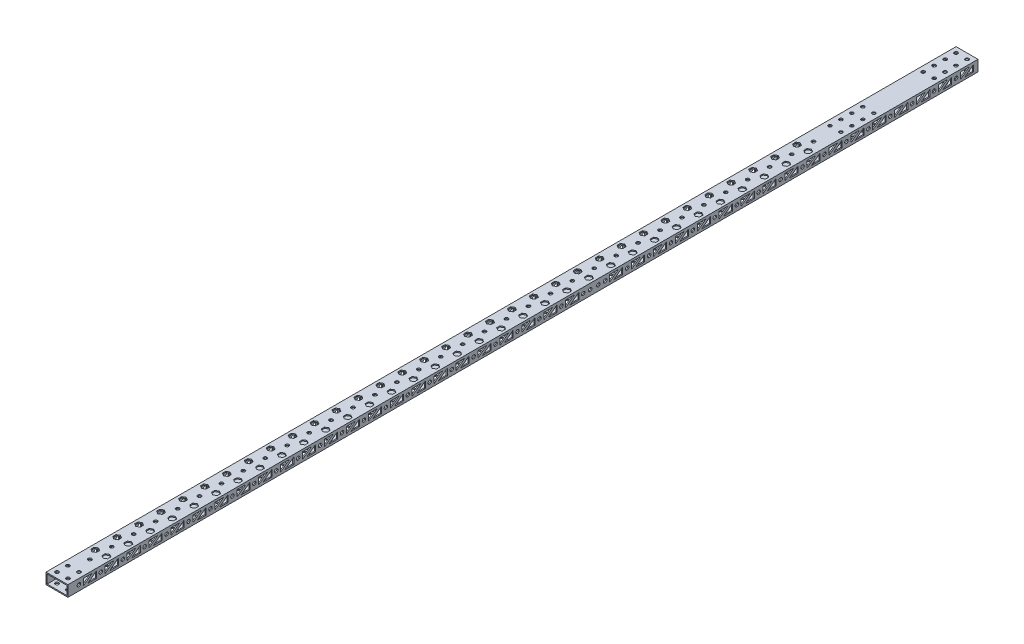
SolidWorks part; units mm, degrees
ref_plane "前视基准面" through (0, 0, 0) normal (0, 0, 1) x (1, 0, 0)
ref_plane "上视基准面" through (0, 0, 0) normal (0, 1, 0) x (1, 0, 0)
ref_plane "右视基准面" through (0, 0, 0) normal (1, 0, 0) x (0, 0, -1)
other "Configuration Table"
sketch "草图1" plane through (0, 0, 0) normal (0, 0, 1) x (1, 0, 0)
  line L1 (0, 0) -> (20, 0)
  line L2 (0, 0) -> (0, -10)
  line L3 (0, -10) -> (20, -10)
  line L4 (20, 0) -> (20, -10)
  dimension "D1" = 20
  dimension "D2" = 10
extrude "拉伸-薄壁1" add sketch "草图1" along normal blind 830 thin thin type one direction reverse wall 1
sketch "草图2" plane through (0, -10, 0) normal (0, -1, 0) x (1, 0, 0)
  line L0 (20, 10) -> (0, 10) construction
  line L1 (20, 830) -> (20, 0) construction
  line L2 (0, 830) -> (0, 0) construction
  line L3 (10, 0) -> (10, 10) construction
  line L4 (0, 0) -> (20, 0) construction
  line L5 (10, 10) -> (10, 140) construction
  line L6 (0, 415) -> (20, 415) construction
  line L7 (10, 830) -> (10, 820) construction
  line L8 (20, 820) -> (0, 820) construction
  line L9 (0, 115) -> (20, 115) construction
  line L10 (20, 105) -> (0, 105) construction
  line L11 (0, 20) -> (20, 20) construction
  line L12 (10, 800) -> (10, 780) construction
  line L13 (15.0981, 787) -> (17.6962, 788.5)
  line L14 (17.6962, 788.5) -> (17.6962, 791.5)
  line L15 (17.6962, 791.5) -> (15.0981, 793)
  line L16 (15.0981, 793) -> (12.5, 791.5)
  line L17 (12.5, 791.5) -> (12.5, 788.5)
  line L18 (12.5, 788.5) -> (15.0981, 787)
  line L19 (15.0981, 790) -> (10, 790) construction
  line L20 (7.5, 788.5) -> (4.9019, 787)
  line L21 (7.5, 791.5) -> (7.5, 788.5)
  line L22 (4.9019, 793) -> (7.5, 791.5)
  line L23 (2.3038, 791.5) -> (4.9019, 793)
  line L24 (2.3038, 788.5) -> (2.3038, 791.5)
  line L25 (4.9019, 787) -> (2.3038, 788.5)
  line L26 (2.3038, 771.5) -> (4.9019, 773)
  line L27 (4.9019, 773) -> (7.5, 771.5)
  line L28 (4.9019, 767) -> (2.3038, 768.5)
  line L29 (2.3038, 768.5) -> (2.3038, 771.5)
  line L30 (7.5, 768.5) -> (4.9019, 767)
  line L31 (7.5, 771.5) -> (7.5, 768.5)
  line L32 (15.0981, 773) -> (12.5, 771.5)
  line L33 (17.6962, 771.5) -> (15.0981, 773)
  line L34 (17.6962, 768.5) -> (17.6962, 771.5)
  line L35 (15.0981, 767) -> (17.6962, 768.5)
  line L36 (12.5, 768.5) -> (15.0981, 767)
  line L37 (12.5, 771.5) -> (12.5, 768.5)
  line L38 (2.3038, 751.5) -> (4.9019, 753)
  line L39 (4.9019, 753) -> (7.5, 751.5)
  line L40 (4.9019, 747) -> (2.3038, 748.5)
  line L41 (2.3038, 748.5) -> (2.3038, 751.5)
  line L42 (7.5, 748.5) -> (4.9019, 747)
  line L43 (7.5, 751.5) -> (7.5, 748.5)
  line L44 (15.0981, 753) -> (12.5, 751.5)
  line L45 (17.6962, 751.5) -> (15.0981, 753)
  line L46 (17.6962, 748.5) -> (17.6962, 751.5)
  line L47 (15.0981, 747) -> (17.6962, 748.5)
  line L48 (12.5, 748.5) -> (15.0981, 747)
  line L49 (12.5, 751.5) -> (12.5, 748.5)
  line L50 (2.3038, 731.5) -> (4.9019, 733)
  line L51 (4.9019, 733) -> (7.5, 731.5)
  line L52 (4.9019, 727) -> (2.3038, 728.5)
  line L53 (2.3038, 728.5) -> (2.3038, 731.5)
  line L54 (7.5, 728.5) -> (4.9019, 727)
  line L55 (7.5, 731.5) -> (7.5, 728.5)
  line L56 (15.0981, 733) -> (12.5, 731.5)
  line L57 (17.6962, 731.5) -> (15.0981, 733)
  line L58 (17.6962, 728.5) -> (17.6962, 731.5)
  line L59 (15.0981, 727) -> (17.6962, 728.5)
  line L60 (12.5, 728.5) -> (15.0981, 727)
  line L61 (12.5, 731.5) -> (12.5, 728.5)
  line L62 (2.3038, 711.5) -> (4.9019, 713)
  line L63 (4.9019, 713) -> (7.5, 711.5)
  line L64 (4.9019, 707) -> (2.3038, 708.5)
  line L65 (2.3038, 708.5) -> (2.3038, 711.5)
  line L66 (7.5, 708.5) -> (4.9019, 707)
  line L67 (7.5, 711.5) -> (7.5, 708.5)
  line L68 (15.0981, 713) -> (12.5, 711.5)
  line L69 (17.6962, 711.5) -> (15.0981, 713)
  line L70 (17.6962, 708.5) -> (17.6962, 711.5)
  line L71 (15.0981, 707) -> (17.6962, 708.5)
  line L72 (12.5, 708.5) -> (15.0981, 707)
  line L73 (12.5, 711.5) -> (12.5, 708.5)
  line L74 (2.3038, 691.5) -> (4.9019, 693)
  line L75 (4.9019, 693) -> (7.5, 691.5)
  line L76 (4.9019, 687) -> (2.3038, 688.5)
  line L77 (2.3038, 688.5) -> (2.3038, 691.5)
  line L78 (7.5, 688.5) -> (4.9019, 687)
  line L79 (7.5, 691.5) -> (7.5, 688.5)
  line L80 (15.0981, 693) -> (12.5, 691.5)
  line L81 (17.6962, 691.5) -> (15.0981, 693)
  line L82 (17.6962, 688.5) -> (17.6962, 691.5)
  line L83 (15.0981, 687) -> (17.6962, 688.5)
  line L84 (12.5, 688.5) -> (15.0981, 687)
  line L85 (12.5, 691.5) -> (12.5, 688.5)
  line L86 (2.3038, 671.5) -> (4.9019, 673)
  line L87 (4.9019, 673) -> (7.5, 671.5)
  line L88 (4.9019, 667) -> (2.3038, 668.5)
  line L89 (2.3038, 668.5) -> (2.3038, 671.5)
  line L90 (7.5, 668.5) -> (4.9019, 667)
  line L91 (7.5, 671.5) -> (7.5, 668.5)
  line L92 (15.0981, 673) -> (12.5, 671.5)
  line L93 (17.6962, 671.5) -> (15.0981, 673)
  line L94 (17.6962, 668.5) -> (17.6962, 671.5)
  line L95 (15.0981, 667) -> (17.6962, 668.5)
  line L96 (12.5, 668.5) -> (15.0981, 667)
  line L97 (12.5, 671.5) -> (12.5, 668.5)
  line L98 (2.3038, 651.5) -> (4.9019, 653)
  line L99 (4.9019, 653) -> (7.5, 651.5)
  line L100 (4.9019, 647) -> (2.3038, 648.5)
  line L101 (2.3038, 648.5) -> (2.3038, 651.5)
  line L102 (7.5, 648.5) -> (4.9019, 647)
  line L103 (7.5, 651.5) -> (7.5, 648.5)
  line L104 (15.0981, 653) -> (12.5, 651.5)
  line L105 (17.6962, 651.5) -> (15.0981, 653)
  line L106 (17.6962, 648.5) -> (17.6962, 651.5)
  line L107 (15.0981, 647) -> (17.6962, 648.5)
  line L108 (12.5, 648.5) -> (15.0981, 647)
  line L109 (12.5, 651.5) -> (12.5, 648.5)
  line L110 (2.3038, 631.5) -> (4.9019, 633)
  line L111 (4.9019, 633) -> (7.5, 631.5)
  line L112 (4.9019, 627) -> (2.3038, 628.5)
  line L113 (2.3038, 628.5) -> (2.3038, 631.5)
  line L114 (7.5, 628.5) -> (4.9019, 627)
  line L115 (7.5, 631.5) -> (7.5, 628.5)
  line L116 (15.0981, 633) -> (12.5, 631.5)
  line L117 (17.6962, 631.5) -> (15.0981, 633)
  line L118 (17.6962, 628.5) -> (17.6962, 631.5)
  line L119 (15.0981, 627) -> (17.6962, 628.5)
  line L120 (12.5, 628.5) -> (15.0981, 627)
  line L121 (12.5, 631.5) -> (12.5, 628.5)
  line L122 (2.3038, 611.5) -> (4.9019, 613)
  line L123 (4.9019, 613) -> (7.5, 611.5)
  line L124 (4.9019, 607) -> (2.3038, 608.5)
  line L125 (2.3038, 608.5) -> (2.3038, 611.5)
  line L126 (7.5, 608.5) -> (4.9019, 607)
  line L127 (7.5, 611.5) -> (7.5, 608.5)
  line L128 (15.0981, 613) -> (12.5, 611.5)
  line L129 (17.6962, 611.5) -> (15.0981, 613)
  line L130 (17.6962, 608.5) -> (17.6962, 611.5)
  line L131 (15.0981, 607) -> (17.6962, 608.5)
  line L132 (12.5, 608.5) -> (15.0981, 607)
  line L133 (12.5, 611.5) -> (12.5, 608.5)
  line L134 (2.3038, 591.5) -> (4.9019, 593)
  line L135 (4.9019, 593) -> (7.5, 591.5)
  line L136 (4.9019, 587) -> (2.3038, 588.5)
  line L137 (2.3038, 588.5) -> (2.3038, 591.5)
  line L138 (7.5, 588.5) -> (4.9019, 587)
  line L139 (7.5, 591.5) -> (7.5, 588.5)
  line L140 (15.0981, 593) -> (12.5, 591.5)
  line L141 (17.6962, 591.5) -> (15.0981, 593)
  line L142 (17.6962, 588.5) -> (17.6962, 591.5)
  line L143 (15.0981, 587) -> (17.6962, 588.5)
  line L144 (12.5, 588.5) -> (15.0981, 587)
  line L145 (12.5, 591.5) -> (12.5, 588.5)
  line L146 (2.3038, 571.5) -> (4.9019, 573)
  line L147 (4.9019, 573) -> (7.5, 571.5)
  line L148 (4.9019, 567) -> (2.3038, 568.5)
  line L149 (2.3038, 568.5) -> (2.3038, 571.5)
  line L150 (7.5, 568.5) -> (4.9019, 567)
  line L151 (7.5, 571.5) -> (7.5, 568.5)
  line L152 (15.0981, 573) -> (12.5, 571.5)
  line L153 (17.6962, 571.5) -> (15.0981, 573)
  line L154 (17.6962, 568.5) -> (17.6962, 571.5)
  line L155 (15.0981, 567) -> (17.6962, 568.5)
  line L156 (12.5, 568.5) -> (15.0981, 567)
  line L157 (12.5, 571.5) -> (12.5, 568.5)
  line L158 (2.3038, 551.5) -> (4.9019, 553)
  line L159 (4.9019, 553) -> (7.5, 551.5)
  line L160 (4.9019, 547) -> (2.3038, 548.5)
  line L161 (2.3038, 548.5) -> (2.3038, 551.5)
  line L162 (7.5, 548.5) -> (4.9019, 547)
  line L163 (7.5, 551.5) -> (7.5, 548.5)
  line L164 (15.0981, 553) -> (12.5, 551.5)
  line L165 (17.6962, 551.5) -> (15.0981, 553)
  line L166 (17.6962, 548.5) -> (17.6962, 551.5)
  line L167 (15.0981, 547) -> (17.6962, 548.5)
  line L168 (12.5, 548.5) -> (15.0981, 547)
  line L169 (12.5, 551.5) -> (12.5, 548.5)
  line L170 (2.3038, 531.5) -> (4.9019, 533)
  line L171 (4.9019, 533) -> (7.5, 531.5)
  line L172 (4.9019, 527) -> (2.3038, 528.5)
  line L173 (2.3038, 528.5) -> (2.3038, 531.5)
  line L174 (7.5, 528.5) -> (4.9019, 527)
  line L175 (7.5, 531.5) -> (7.5, 528.5)
  line L176 (15.0981, 533) -> (12.5, 531.5)
  line L177 (17.6962, 531.5) -> (15.0981, 533)
  line L178 (17.6962, 528.5) -> (17.6962, 531.5)
  line L179 (15.0981, 527) -> (17.6962, 528.5)
  line L180 (12.5, 528.5) -> (15.0981, 527)
  line L181 (12.5, 531.5) -> (12.5, 528.5)
  line L182 (2.3038, 511.5) -> (4.9019, 513)
  line L183 (4.9019, 513) -> (7.5, 511.5)
  line L184 (4.9019, 507) -> (2.3038, 508.5)
  line L185 (2.3038, 508.5) -> (2.3038, 511.5)
  line L186 (7.5, 508.5) -> (4.9019, 507)
  line L187 (7.5, 511.5) -> (7.5, 508.5)
  line L188 (15.0981, 513) -> (12.5, 511.5)
  line L189 (17.6962, 511.5) -> (15.0981, 513)
  line L190 (17.6962, 508.5) -> (17.6962, 511.5)
  line L191 (15.0981, 507) -> (17.6962, 508.5)
  line L192 (12.5, 508.5) -> (15.0981, 507)
  line L193 (12.5, 511.5) -> (12.5, 508.5)
  line L194 (2.3038, 491.5) -> (4.9019, 493)
  line L195 (4.9019, 493) -> (7.5, 491.5)
  line L196 (4.9019, 487) -> (2.3038, 488.5)
  line L197 (2.3038, 488.5) -> (2.3038, 491.5)
  line L198 (7.5, 488.5) -> (4.9019, 487)
  line L199 (7.5, 491.5) -> (7.5, 488.5)
  line L200 (15.0981, 493) -> (12.5, 491.5)
  line L201 (17.6962, 491.5) -> (15.0981, 493)
  line L202 (17.6962, 488.5) -> (17.6962, 491.5)
  line L203 (15.0981, 487) -> (17.6962, 488.5)
  line L204 (12.5, 488.5) -> (15.0981, 487)
  line L205 (12.5, 491.5) -> (12.5, 488.5)
  line L206 (2.3038, 471.5) -> (4.9019, 473)
  line L207 (4.9019, 473) -> (7.5, 471.5)
  line L208 (4.9019, 467) -> (2.3038, 468.5)
  line L209 (2.3038, 468.5) -> (2.3038, 471.5)
  line L210 (7.5, 468.5) -> (4.9019, 467)
  line L211 (7.5, 471.5) -> (7.5, 468.5)
  line L212 (15.0981, 473) -> (12.5, 471.5)
  line L213 (17.6962, 471.5) -> (15.0981, 473)
  line L214 (17.6962, 468.5) -> (17.6962, 471.5)
  line L215 (15.0981, 467) -> (17.6962, 468.5)
  line L216 (12.5, 468.5) -> (15.0981, 467)
  line L217 (12.5, 471.5) -> (12.5, 468.5)
  line L218 (2.3038, 451.5) -> (4.9019, 453)
  line L219 (4.9019, 453) -> (7.5, 451.5)
  line L220 (4.9019, 447) -> (2.3038, 448.5)
  line L221 (2.3038, 448.5) -> (2.3038, 451.5)
  line L222 (7.5, 448.5) -> (4.9019, 447)
  line L223 (7.5, 451.5) -> (7.5, 448.5)
  line L224 (15.0981, 453) -> (12.5, 451.5)
  line L225 (17.6962, 451.5) -> (15.0981, 453)
  line L226 (17.6962, 448.5) -> (17.6962, 451.5)
  line L227 (15.0981, 447) -> (17.6962, 448.5)
  line L228 (12.5, 448.5) -> (15.0981, 447)
  line L229 (12.5, 451.5) -> (12.5, 448.5)
  line L230 (2.3038, 431.5) -> (4.9019, 433)
  line L231 (4.9019, 433) -> (7.5, 431.5)
  line L232 (4.9019, 427) -> (2.3038, 428.5)
  line L233 (2.3038, 428.5) -> (2.3038, 431.5)
  line L234 (7.5, 428.5) -> (4.9019, 427)
  line L235 (7.5, 431.5) -> (7.5, 428.5)
  line L236 (15.0981, 433) -> (12.5, 431.5)
  line L237 (17.6962, 431.5) -> (15.0981, 433)
  line L238 (17.6962, 428.5) -> (17.6962, 431.5)
  line L239 (15.0981, 427) -> (17.6962, 428.5)
  line L240 (12.5, 428.5) -> (15.0981, 427)
  line L241 (12.5, 431.5) -> (12.5, 428.5)
  line L242 (2.3038, 411.5) -> (4.9019, 413)
  line L243 (4.9019, 413) -> (7.5, 411.5)
  line L244 (4.9019, 407) -> (2.3038, 408.5)
  line L245 (2.3038, 408.5) -> (2.3038, 411.5)
  line L246 (7.5, 408.5) -> (4.9019, 407)
  line L247 (7.5, 411.5) -> (7.5, 408.5)
  line L248 (15.0981, 413) -> (12.5, 411.5)
  line L249 (17.6962, 411.5) -> (15.0981, 413)
  line L250 (17.6962, 408.5) -> (17.6962, 411.5)
  line L251 (15.0981, 407) -> (17.6962, 408.5)
  line L252 (12.5, 408.5) -> (15.0981, 407)
  line L253 (12.5, 411.5) -> (12.5, 408.5)
  line L254 (2.3038, 391.5) -> (4.9019, 393)
  line L255 (4.9019, 393) -> (7.5, 391.5)
  line L256 (4.9019, 387) -> (2.3038, 388.5)
  line L257 (2.3038, 388.5) -> (2.3038, 391.5)
  line L258 (7.5, 388.5) -> (4.9019, 387)
  line L259 (7.5, 391.5) -> (7.5, 388.5)
  line L260 (15.0981, 393) -> (12.5, 391.5)
  line L261 (17.6962, 391.5) -> (15.0981, 393)
  line L262 (17.6962, 388.5) -> (17.6962, 391.5)
  line L263 (15.0981, 387) -> (17.6962, 388.5)
  line L264 (12.5, 388.5) -> (15.0981, 387)
  line L265 (12.5, 391.5) -> (12.5, 388.5)
  line L266 (2.3038, 371.5) -> (4.9019, 373)
  line L267 (4.9019, 373) -> (7.5, 371.5)
  line L268 (4.9019, 367) -> (2.3038, 368.5)
  line L269 (2.3038, 368.5) -> (2.3038, 371.5)
  line L270 (7.5, 368.5) -> (4.9019, 367)
  line L271 (7.5, 371.5) -> (7.5, 368.5)
  line L272 (15.0981, 373) -> (12.5, 371.5)
  line L273 (17.6962, 371.5) -> (15.0981, 373)
  line L274 (17.6962, 368.5) -> (17.6962, 371.5)
  line L275 (15.0981, 367) -> (17.6962, 368.5)
  line L276 (12.5, 368.5) -> (15.0981, 367)
  line L277 (12.5, 371.5) -> (12.5, 368.5)
  line L278 (2.3038, 351.5) -> (4.9019, 353)
  line L279 (4.9019, 353) -> (7.5, 351.5)
  line L280 (4.9019, 347) -> (2.3038, 348.5)
  line L281 (2.3038, 348.5) -> (2.3038, 351.5)
  line L282 (7.5, 348.5) -> (4.9019, 347)
  line L283 (7.5, 351.5) -> (7.5, 348.5)
  line L284 (15.0981, 353) -> (12.5, 351.5)
  line L285 (17.6962, 351.5) -> (15.0981, 353)
  line L286 (17.6962, 348.5) -> (17.6962, 351.5)
  line L287 (15.0981, 347) -> (17.6962, 348.5)
  line L288 (12.5, 348.5) -> (15.0981, 347)
  line L289 (12.5, 351.5) -> (12.5, 348.5)
  line L290 (2.3038, 331.5) -> (4.9019, 333)
  line L291 (4.9019, 333) -> (7.5, 331.5)
  line L292 (4.9019, 327) -> (2.3038, 328.5)
  line L293 (2.3038, 328.5) -> (2.3038, 331.5)
  line L294 (7.5, 328.5) -> (4.9019, 327)
  line L295 (7.5, 331.5) -> (7.5, 328.5)
  line L296 (15.0981, 333) -> (12.5, 331.5)
  line L297 (17.6962, 331.5) -> (15.0981, 333)
  line L298 (17.6962, 328.5) -> (17.6962, 331.5)
  line L299 (15.0981, 327) -> (17.6962, 328.5)
  line L300 (12.5, 328.5) -> (15.0981, 327)
  line L301 (12.5, 331.5) -> (12.5, 328.5)
  line L302 (2.3038, 311.5) -> (4.9019, 313)
  line L303 (4.9019, 313) -> (7.5, 311.5)
  line L304 (4.9019, 307) -> (2.3038, 308.5)
  line L305 (2.3038, 308.5) -> (2.3038, 311.5)
  line L306 (7.5, 308.5) -> (4.9019, 307)
  line L307 (7.5, 311.5) -> (7.5, 308.5)
  line L308 (15.0981, 313) -> (12.5, 311.5)
  line L309 (17.6962, 311.5) -> (15.0981, 313)
  line L310 (17.6962, 308.5) -> (17.6962, 311.5)
  line L311 (15.0981, 307) -> (17.6962, 308.5)
  line L312 (12.5, 308.5) -> (15.0981, 307)
  line L313 (12.5, 311.5) -> (12.5, 308.5)
  line L314 (2.3038, 291.5) -> (4.9019, 293)
  line L315 (4.9019, 293) -> (7.5, 291.5)
  line L316 (4.9019, 287) -> (2.3038, 288.5)
  line L317 (2.3038, 288.5) -> (2.3038, 291.5)
  line L318 (7.5, 288.5) -> (4.9019, 287)
  line L319 (7.5, 291.5) -> (7.5, 288.5)
  line L320 (15.0981, 293) -> (12.5, 291.5)
  line L321 (17.6962, 291.5) -> (15.0981, 293)
  line L322 (17.6962, 288.5) -> (17.6962, 291.5)
  line L323 (15.0981, 287) -> (17.6962, 288.5)
  line L324 (12.5, 288.5) -> (15.0981, 287)
  line L325 (12.5, 291.5) -> (12.5, 288.5)
  line L326 (2.3038, 271.5) -> (4.9019, 273)
  line L327 (4.9019, 273) -> (7.5, 271.5)
  line L328 (4.9019, 267) -> (2.3038, 268.5)
  line L329 (2.3038, 268.5) -> (2.3038, 271.5)
  line L330 (7.5, 268.5) -> (4.9019, 267)
  line L331 (7.5, 271.5) -> (7.5, 268.5)
  line L332 (15.0981, 273) -> (12.5, 271.5)
  line L333 (17.6962, 271.5) -> (15.0981, 273)
  line L334 (17.6962, 268.5) -> (17.6962, 271.5)
  line L335 (15.0981, 267) -> (17.6962, 268.5)
  line L336 (12.5, 268.5) -> (15.0981, 267)
  line L337 (12.5, 271.5) -> (12.5, 268.5)
  line L338 (2.3038, 251.5) -> (4.9019, 253)
  line L339 (4.9019, 253) -> (7.5, 251.5)
  line L340 (4.9019, 247) -> (2.3038, 248.5)
  line L341 (2.3038, 248.5) -> (2.3038, 251.5)
  line L342 (7.5, 248.5) -> (4.9019, 247)
  line L343 (7.5, 251.5) -> (7.5, 248.5)
  line L344 (15.0981, 253) -> (12.5, 251.5)
  line L345 (17.6962, 251.5) -> (15.0981, 253)
  line L346 (17.6962, 248.5) -> (17.6962, 251.5)
  line L347 (15.0981, 247) -> (17.6962, 248.5)
  line L348 (12.5, 248.5) -> (15.0981, 247)
  line L349 (12.5, 251.5) -> (12.5, 248.5)
  line L350 (2.3038, 231.5) -> (4.9019, 233)
  line L351 (4.9019, 233) -> (7.5, 231.5)
  line L352 (4.9019, 227) -> (2.3038, 228.5)
  line L353 (2.3038, 228.5) -> (2.3038, 231.5)
  line L354 (7.5, 228.5) -> (4.9019, 227)
  line L355 (7.5, 231.5) -> (7.5, 228.5)
  line L356 (15.0981, 233) -> (12.5, 231.5)
  line L357 (17.6962, 231.5) -> (15.0981, 233)
  line L358 (17.6962, 228.5) -> (17.6962, 231.5)
  line L359 (15.0981, 227) -> (17.6962, 228.5)
  line L360 (12.5, 228.5) -> (15.0981, 227)
  line L361 (12.5, 231.5) -> (12.5, 228.5)
  line L362 (2.3038, 211.5) -> (4.9019, 213)
  line L363 (4.9019, 213) -> (7.5, 211.5)
  line L364 (4.9019, 207) -> (2.3038, 208.5)
  line L365 (2.3038, 208.5) -> (2.3038, 211.5)
  line L366 (7.5, 208.5) -> (4.9019, 207)
  line L367 (7.5, 211.5) -> (7.5, 208.5)
  line L368 (15.0981, 213) -> (12.5, 211.5)
  line L369 (17.6962, 211.5) -> (15.0981, 213)
  line L370 (17.6962, 208.5) -> (17.6962, 211.5)
  line L371 (15.0981, 207) -> (17.6962, 208.5)
  line L372 (12.5, 208.5) -> (15.0981, 207)
  line L373 (12.5, 211.5) -> (12.5, 208.5)
  line L374 (2.3038, 191.5) -> (4.9019, 193)
  line L375 (4.9019, 193) -> (7.5, 191.5)
  line L376 (4.9019, 187) -> (2.3038, 188.5)
  line L377 (2.3038, 188.5) -> (2.3038, 191.5)
  line L378 (7.5, 188.5) -> (4.9019, 187)
  line L379 (7.5, 191.5) -> (7.5, 188.5)
  line L380 (15.0981, 193) -> (12.5, 191.5)
  line L381 (17.6962, 191.5) -> (15.0981, 193)
  line L382 (17.6962, 188.5) -> (17.6962, 191.5)
  line L383 (15.0981, 187) -> (17.6962, 188.5)
  line L384 (12.5, 188.5) -> (15.0981, 187)
  line L385 (12.5, 191.5) -> (12.5, 188.5)
  line L386 (2.3038, 171.5) -> (4.9019, 173)
  line L387 (4.9019, 173) -> (7.5, 171.5)
  line L388 (4.9019, 167) -> (2.3038, 168.5)
  line L389 (2.3038, 168.5) -> (2.3038, 171.5)
  line L390 (7.5, 168.5) -> (4.9019, 167)
  line L391 (7.5, 171.5) -> (7.5, 168.5)
  line L392 (15.0981, 173) -> (12.5, 171.5)
  line L393 (17.6962, 171.5) -> (15.0981, 173)
  line L394 (17.6962, 168.5) -> (17.6962, 171.5)
  line L395 (15.0981, 167) -> (17.6962, 168.5)
  line L396 (12.5, 168.5) -> (15.0981, 167)
  line L397 (12.5, 171.5) -> (12.5, 168.5)
  line L398 (2.3038, 151.5) -> (4.9019, 153)
  line L399 (4.9019, 153) -> (7.5, 151.5)
  line L400 (4.9019, 147) -> (2.3038, 148.5)
  line L401 (2.3038, 148.5) -> (2.3038, 151.5)
  line L402 (7.5, 148.5) -> (4.9019, 147)
  line L403 (7.5, 151.5) -> (7.5, 148.5)
  line L404 (15.0981, 153) -> (12.5, 151.5)
  line L405 (17.6962, 151.5) -> (15.0981, 153)
  line L406 (17.6962, 148.5) -> (17.6962, 151.5)
  line L407 (15.0981, 147) -> (17.6962, 148.5)
  line L408 (12.5, 148.5) -> (15.0981, 147)
  line L409 (12.5, 151.5) -> (12.5, 148.5)
  circle A0 centre (5, 5) radius 1.575
  circle A1 centre (15, 5) radius 1.575
  circle A2 centre (15, 15) radius 1.575
  circle A3 centre (5, 15) radius 1.575
  circle A4 centre (10, 140) radius 1.575
  circle A5 centre (10, 160) radius 1.575
  circle A6 centre (10, 180) radius 1.575
  circle A7 centre (10, 200) radius 1.575
  circle A8 centre (10, 220) radius 1.575
  circle A9 centre (10, 240) radius 1.575
  circle A10 centre (10, 260) radius 1.575
  circle A11 centre (10, 280) radius 1.575
  circle A12 centre (10, 300) radius 1.575
  circle A13 centre (10, 320) radius 1.575
  circle A14 centre (10, 340) radius 1.575
  circle A15 centre (10, 360) radius 1.575
  circle A16 centre (10, 380) radius 1.575
  circle A17 centre (10, 400) radius 1.575
  circle A18 centre (10, 420) radius 1.575
  circle A19 centre (10, 440) radius 1.575
  circle A20 centre (10, 460) radius 1.575
  circle A21 centre (10, 480) radius 1.575
  circle A22 centre (10, 500) radius 1.575
  circle A23 centre (10, 520) radius 1.575
  circle A24 centre (10, 540) radius 1.575
  circle A25 centre (10, 560) radius 1.575
  circle A26 centre (10, 580) radius 1.575
  circle A27 centre (10, 600) radius 1.575
  circle A28 centre (10, 620) radius 1.575
  circle A29 centre (10, 640) radius 1.575
  circle A30 centre (10, 660) radius 1.575
  circle A31 centre (10, 680) radius 1.575
  circle A32 centre (10, 700) radius 1.575
  circle A33 centre (10, 720) radius 1.575
  circle A34 centre (10, 740) radius 1.575
  circle A37 centre (5, 815) radius 1.575
  circle A38 centre (15, 815) radius 1.575
  circle A39 centre (15, 825) radius 1.575
  circle A40 centre (5, 825) radius 1.575
  circle A41 centre (10, 760) radius 1.575
  circle A42 centre (10, 780) radius 1.575
  circle A43 centre (10, 800) radius 1.575
  circle A44 centre (5, 120) radius 1.5
  circle A45 centre (15, 120) radius 1.5
  circle A46 centre (15, 110) radius 1.5
  circle A47 centre (5, 110) radius 1.5
  circle A48 centre (5, 100) radius 1.5
  circle A49 centre (15, 100) radius 1.5
  circle A50 centre (15, 90) radius 1.5
  circle A51 centre (5, 90) radius 1.5
  circle A52 centre (5, 25) radius 1.575
  circle A53 centre (15, 25) radius 1.575
  circle A54 centre (15, 35) radius 1.575
  circle A55 centre (5, 35) radius 1.575
  circle A56 centre (15.0981, 790) radius 2.5981 construction
  circle A57 centre (4.9019, 790) radius 2.5981 construction
  dimension "D1" = 3.15
  dimension "D5" = 3.15
  dimension "D10" = 3
  dimension "D2" = 5
  dimension "D3" = 5
  dimension "D4" = 10
  dimension "D6" = 130
  dimension "D8" = 20
  dimension "D9" = 115
  dimension "D11" = 5
  dimension "D12" = 5
  dimension "D13" = 10
  dimension "D14" = 10
  dimension "D15" = 3
  dimension "D16" = 2.5
  dimension "D17" = 33
  dimension "D18" = 20
  dimension "D7" = 34
extrude "切除-拉伸1" cut sketch "草图2" against normal through all
sketch "草图4" plane through (20, 0, 0) normal (1, 0, 0) x (0, 0, -1)
  line L0 (0, -5) -> (-830, -5) construction
  line L1 (0, -10) -> (0, 0) construction
  line L2 (-830, -10) -> (-830, 0) construction
  line L3 (-4, -2) -> (-4, -8)
  line L4 (-4, -8) -> (-12, -8)
  line L5 (-12, -8) -> (-4, -2)
  line L6 (-8, -2) -> (-16, -8)
  line L7 (-16, -8) -> (-16, -2)
  line L8 (-16, -2) -> (-8, -2)
  line L9 (-830, -10) -> (0, -10) construction
  line L10 (-830, 0) -> (0, 0) construction
  line L11 (-24, -2) -> (-24, -8)
  line L12 (-24, -8) -> (-32, -8)
  line L13 (-32, -8) -> (-24, -2)
  line L14 (-36, -2) -> (-28, -2)
  line L15 (-28, -2) -> (-36, -8)
  line L16 (-36, -8) -> (-36, -2)
  line L17 (-44, -2) -> (-44, -8)
  line L18 (-44, -8) -> (-52, -8)
  line L19 (-52, -8) -> (-44, -2)
  line L20 (-56, -2) -> (-48, -2)
  line L21 (-48, -2) -> (-56, -8)
  line L22 (-56, -8) -> (-56, -2)
  line L23 (-64, -2) -> (-64, -8)
  line L24 (-64, -8) -> (-72, -8)
  line L25 (-72, -8) -> (-64, -2)
  line L26 (-76, -2) -> (-68, -2)
  line L27 (-68, -2) -> (-76, -8)
  line L28 (-76, -8) -> (-76, -2)
  line L29 (-84, -2) -> (-84, -8)
  line L30 (-84, -8) -> (-92, -8)
  line L31 (-92, -8) -> (-84, -2)
  line L32 (-96, -2) -> (-88, -2)
  line L33 (-88, -2) -> (-96, -8)
  line L34 (-96, -8) -> (-96, -2)
  line L35 (-104, -2) -> (-104, -8)
  line L36 (-104, -8) -> (-112, -8)
  line L37 (-112, -8) -> (-104, -2)
  line L38 (-116, -2) -> (-108, -2)
  line L39 (-108, -2) -> (-116, -8)
  line L40 (-116, -8) -> (-116, -2)
  line L41 (-124, -2) -> (-124, -8)
  line L42 (-124, -8) -> (-132, -8)
  line L43 (-132, -8) -> (-124, -2)
  line L44 (-136, -2) -> (-128, -2)
  line L45 (-128, -2) -> (-136, -8)
  line L46 (-136, -8) -> (-136, -2)
  line L47 (-144, -2) -> (-144, -8)
  line L48 (-144, -8) -> (-152, -8)
  line L49 (-152, -8) -> (-144, -2)
  line L50 (-156, -2) -> (-148, -2)
  line L51 (-148, -2) -> (-156, -8)
  line L52 (-156, -8) -> (-156, -2)
  line L53 (-164, -2) -> (-164, -8)
  line L54 (-164, -8) -> (-172, -8)
  line L55 (-172, -8) -> (-164, -2)
  line L56 (-176, -2) -> (-168, -2)
  line L57 (-168, -2) -> (-176, -8)
  line L58 (-176, -8) -> (-176, -2)
  line L59 (-184, -2) -> (-184, -8)
  line L60 (-184, -8) -> (-192, -8)
  line L61 (-192, -8) -> (-184, -2)
  line L62 (-196, -2) -> (-188, -2)
  line L63 (-188, -2) -> (-196, -8)
  line L64 (-196, -8) -> (-196, -2)
  line L65 (-204, -2) -> (-204, -8)
  line L66 (-204, -8) -> (-212, -8)
  line L67 (-212, -8) -> (-204, -2)
  line L68 (-216, -2) -> (-208, -2)
  line L69 (-208, -2) -> (-216, -8)
  line L70 (-216, -8) -> (-216, -2)
  line L71 (-224, -2) -> (-224, -8)
  line L72 (-224, -8) -> (-232, -8)
  line L73 (-232, -8) -> (-224, -2)
  line L74 (-236, -2) -> (-228, -2)
  line L75 (-228, -2) -> (-236, -8)
  line L76 (-236, -8) -> (-236, -2)
  line L77 (-244, -2) -> (-244, -8)
  line L78 (-244, -8) -> (-252, -8)
  line L79 (-252, -8) -> (-244, -2)
  line L80 (-256, -2) -> (-248, -2)
  line L81 (-248, -2) -> (-256, -8)
  line L82 (-256, -8) -> (-256, -2)
  line L83 (-264, -2) -> (-264, -8)
  line L84 (-264, -8) -> (-272, -8)
  line L85 (-272, -8) -> (-264, -2)
  line L86 (-276, -2) -> (-268, -2)
  line L87 (-268, -2) -> (-276, -8)
  line L88 (-276, -8) -> (-276, -2)
  line L89 (-284, -2) -> (-284, -8)
  line L90 (-284, -8) -> (-292, -8)
  line L91 (-292, -8) -> (-284, -2)
  line L92 (-296, -2) -> (-288, -2)
  line L93 (-288, -2) -> (-296, -8)
  line L94 (-296, -8) -> (-296, -2)
  line L95 (-304, -2) -> (-304, -8)
  line L96 (-304, -8) -> (-312, -8)
  line L97 (-312, -8) -> (-304, -2)
  line L98 (-316, -2) -> (-308, -2)
  line L99 (-308, -2) -> (-316, -8)
  line L100 (-316, -8) -> (-316, -2)
  line L101 (-324, -2) -> (-324, -8)
  line L102 (-324, -8) -> (-332, -8)
  line L103 (-332, -8) -> (-324, -2)
  line L104 (-336, -2) -> (-328, -2)
  line L105 (-328, -2) -> (-336, -8)
  line L106 (-336, -8) -> (-336, -2)
  line L113 (-364, -2) -> (-364, -8)
  line L114 (-364, -8) -> (-372, -8)
  line L115 (-372, -8) -> (-364, -2)
  line L116 (-376, -2) -> (-368, -2)
  line L117 (-368, -2) -> (-376, -8)
  line L118 (-376, -8) -> (-376, -2)
  line L119 (-384, -2) -> (-384, -8)
  line L120 (-384, -8) -> (-392, -8)
  line L121 (-392, -8) -> (-384, -2)
  line L122 (-396, -2) -> (-388, -2)
  line L123 (-388, -2) -> (-396, -8)
  line L124 (-396, -8) -> (-396, -2)
  line L125 (-404, -2) -> (-404, -8)
  line L126 (-404, -8) -> (-412, -8)
  line L127 (-412, -8) -> (-404, -2)
  line L128 (-416, -2) -> (-408, -2)
  line L129 (-408, -2) -> (-416, -8)
  line L130 (-416, -8) -> (-416, -2)
  line L131 (-424, -2) -> (-424, -8)
  line L132 (-424, -8) -> (-432, -8)
  line L133 (-432, -8) -> (-424, -2)
  line L134 (-436, -2) -> (-428, -2)
  line L135 (-428, -2) -> (-436, -8)
  line L136 (-436, -8) -> (-436, -2)
  line L137 (-444, -2) -> (-444, -8)
  line L138 (-444, -8) -> (-452, -8)
  line L139 (-452, -8) -> (-444, -2)
  line L140 (-456, -2) -> (-448, -2)
  line L141 (-448, -2) -> (-456, -8)
  line L142 (-456, -8) -> (-456, -2)
  line L143 (-464, -2) -> (-464, -8)
  line L144 (-464, -8) -> (-472, -8)
  line L145 (-472, -8) -> (-464, -2)
  line L146 (-476, -2) -> (-468, -2)
  line L147 (-468, -2) -> (-476, -8)
  line L148 (-476, -8) -> (-476, -2)
  line L149 (-484, -2) -> (-484, -8)
  line L150 (-484, -8) -> (-492, -8)
  line L151 (-492, -8) -> (-484, -2)
  line L152 (-496, -2) -> (-488, -2)
  line L153 (-488, -2) -> (-496, -8)
  line L154 (-496, -8) -> (-496, -2)
  line L155 (-504, -2) -> (-504, -8)
  line L156 (-504, -8) -> (-512, -8)
  line L157 (-512, -8) -> (-504, -2)
  line L158 (-516, -2) -> (-508, -2)
  line L159 (-508, -2) -> (-516, -8)
  line L160 (-516, -8) -> (-516, -2)
  line L161 (-524, -2) -> (-524, -8)
  line L162 (-524, -8) -> (-532, -8)
  line L163 (-532, -8) -> (-524, -2)
  line L164 (-536, -2) -> (-528, -2)
  line L165 (-528, -2) -> (-536, -8)
  line L166 (-536, -8) -> (-536, -2)
  line L167 (-544, -2) -> (-544, -8)
  line L168 (-544, -8) -> (-552, -8)
  line L169 (-552, -8) -> (-544, -2)
  line L170 (-556, -2) -> (-548, -2)
  line L171 (-548, -2) -> (-556, -8)
  line L172 (-556, -8) -> (-556, -2)
  line L173 (-564, -2) -> (-564, -8)
  line L174 (-564, -8) -> (-572, -8)
  line L175 (-572, -8) -> (-564, -2)
  line L176 (-576, -2) -> (-568, -2)
  line L177 (-568, -2) -> (-576, -8)
  line L178 (-576, -8) -> (-576, -2)
  line L179 (-584, -2) -> (-584, -8)
  line L180 (-584, -8) -> (-592, -8)
  line L181 (-592, -8) -> (-584, -2)
  line L182 (-596, -2) -> (-588, -2)
  line L183 (-588, -2) -> (-596, -8)
  line L184 (-596, -8) -> (-596, -2)
  line L185 (-604, -2) -> (-604, -8)
  line L186 (-604, -8) -> (-612, -8)
  line L187 (-612, -8) -> (-604, -2)
  line L188 (-616, -2) -> (-608, -2)
  line L189 (-608, -2) -> (-616, -8)
  line L190 (-616, -8) -> (-616, -2)
  line L191 (-624, -2) -> (-624, -8)
  line L192 (-624, -8) -> (-632, -8)
  line L193 (-632, -8) -> (-624, -2)
  line L194 (-636, -2) -> (-628, -2)
  line L195 (-628, -2) -> (-636, -8)
  line L196 (-636, -8) -> (-636, -2)
  line L197 (-644, -2) -> (-644, -8)
  line L198 (-644, -8) -> (-652, -8)
  line L199 (-652, -8) -> (-644, -2)
  line L200 (-656, -2) -> (-648, -2)
  line L201 (-648, -2) -> (-656, -8)
  line L202 (-656, -8) -> (-656, -2)
  line L203 (-664, -2) -> (-664, -8)
  line L204 (-664, -8) -> (-672, -8)
  line L205 (-672, -8) -> (-664, -2)
  line L206 (-676, -2) -> (-668, -2)
  line L207 (-668, -2) -> (-676, -8)
  line L208 (-676, -8) -> (-676, -2)
  line L209 (-684, -2) -> (-684, -8)
  line L210 (-684, -8) -> (-692, -8)
  line L211 (-692, -8) -> (-684, -2)
  line L212 (-696, -2) -> (-688, -2)
  line L213 (-688, -2) -> (-696, -8)
  line L214 (-696, -8) -> (-696, -2)
  line L215 (-704, -2) -> (-704, -8)
  line L216 (-704, -8) -> (-712, -8)
  line L217 (-712, -8) -> (-704, -2)
  line L218 (-716, -2) -> (-708, -2)
  line L219 (-708, -2) -> (-716, -8)
  line L220 (-716, -8) -> (-716, -2)
  line L221 (-724, -2) -> (-724, -8)
  line L222 (-724, -8) -> (-732, -8)
  line L223 (-732, -8) -> (-724, -2)
  line L224 (-736, -2) -> (-728, -2)
  line L225 (-728, -2) -> (-736, -8)
  line L226 (-736, -8) -> (-736, -2)
  line L227 (-744, -2) -> (-744, -8)
  line L228 (-744, -8) -> (-752, -8)
  line L229 (-752, -8) -> (-744, -2)
  line L230 (-756, -2) -> (-748, -2)
  line L231 (-748, -2) -> (-756, -8)
  line L232 (-756, -8) -> (-756, -2)
  line L233 (-764, -2) -> (-764, -8)
  line L234 (-764, -8) -> (-772, -8)
  line L235 (-772, -8) -> (-764, -2)
  line L236 (-776, -2) -> (-768, -2)
  line L237 (-768, -2) -> (-776, -8)
  line L238 (-776, -8) -> (-776, -2)
  line L239 (-784, -2) -> (-784, -8)
  line L240 (-784, -8) -> (-792, -8)
  line L241 (-792, -8) -> (-784, -2)
  line L242 (-796, -2) -> (-788, -2)
  line L243 (-788, -2) -> (-796, -8)
  line L244 (-796, -8) -> (-796, -2)
  line L245 (-804, -2) -> (-804, -8)
  line L246 (-804, -8) -> (-812, -8)
  line L247 (-812, -8) -> (-804, -2)
  line L248 (-816, -2) -> (-808, -2)
  line L249 (-808, -2) -> (-816, -8)
  line L250 (-816, -8) -> (-816, -2)
  line L251 (-350, 0) -> (-350, -10) construction
  line L253 (-344, -2) -> (-344, -8) [skipped]
  line L254 (-344, -8) -> (-352, -8) [skipped]
  line L255 (-352, -8) -> (-344, -2) [skipped]
  line L256 (-356, -2) -> (-348, -2) [skipped]
  line L257 (-348, -2) -> (-356, -8) [skipped]
  line L258 (-356, -8) -> (-356, -2) [skipped]
  circle A0 centre (-20, -5) radius 1.575
  circle A1 centre (-40, -5) radius 1.575
  circle A2 centre (-60, -5) radius 1.575
  circle A3 centre (-80, -5) radius 1.575
  circle A4 centre (-100, -5) radius 1.575
  circle A5 centre (-120, -5) radius 1.575
  circle A6 centre (-140, -5) radius 1.575
  circle A7 centre (-160, -5) radius 1.575
  circle A8 centre (-180, -5) radius 1.575
  circle A9 centre (-200, -5) radius 1.575
  circle A10 centre (-220, -5) radius 1.575
  circle A11 centre (-240, -5) radius 1.575
  circle A12 centre (-260, -5) radius 1.575
  circle A13 centre (-280, -5) radius 1.575
  circle A14 centre (-300, -5) radius 1.575
  circle A15 centre (-320, -5) radius 1.575
  circle A16 centre (-340, -5) radius 1.575
  circle A17 centre (-360, -5) radius 1.575
  circle A18 centre (-380, -5) radius 1.575
  circle A19 centre (-400, -5) radius 1.575
  circle A20 centre (-420, -5) radius 1.575
  circle A21 centre (-440, -5) radius 1.575
  circle A22 centre (-460, -5) radius 1.575
  circle A23 centre (-480, -5) radius 1.575
  circle A24 centre (-500, -5) radius 1.575
  circle A25 centre (-520, -5) radius 1.575
  circle A26 centre (-540, -5) radius 1.575
  circle A27 centre (-560, -5) radius 1.575
  circle A28 centre (-580, -5) radius 1.575
  circle A29 centre (-600, -5) radius 1.575
  circle A30 centre (-620, -5) radius 1.575
  circle A31 centre (-640, -5) radius 1.575
  circle A32 centre (-660, -5) radius 1.575
  circle A33 centre (-680, -5) radius 1.575
  circle A34 centre (-700, -5) radius 1.575
  circle A35 centre (-720, -5) radius 1.575
  circle A36 centre (-740, -5) radius 1.575
  circle A37 centre (-760, -5) radius 1.575
  circle A38 centre (-780, -5) radius 1.575
  circle A39 centre (-800, -5) radius 1.575
  circle A40 centre (-820, -5) radius 1.575
  circle A41 centre (-353.75, -5) radius 1.6
  circle A42 centre (-346.25, -5) radius 1.6
  dimension "D2" = 3.15
  dimension "D15" = 3.2
  dimension "D1" = 20
  dimension "D3" = 20
  dimension "D4" = 8
  dimension "D5" = 6
  dimension "D6" = 6
  dimension "D7" = 2
  dimension "D8" = 2
  dimension "D9" = 12
  dimension "D10" = 4
  dimension "D12" = 20
  dimension "D14" = 350
  dimension "D16" = 3.75
  dimension "D13" = 41
  dimension "D11" = 41
extrude "切除-拉伸2" cut sketch "草图4" against normal through all
